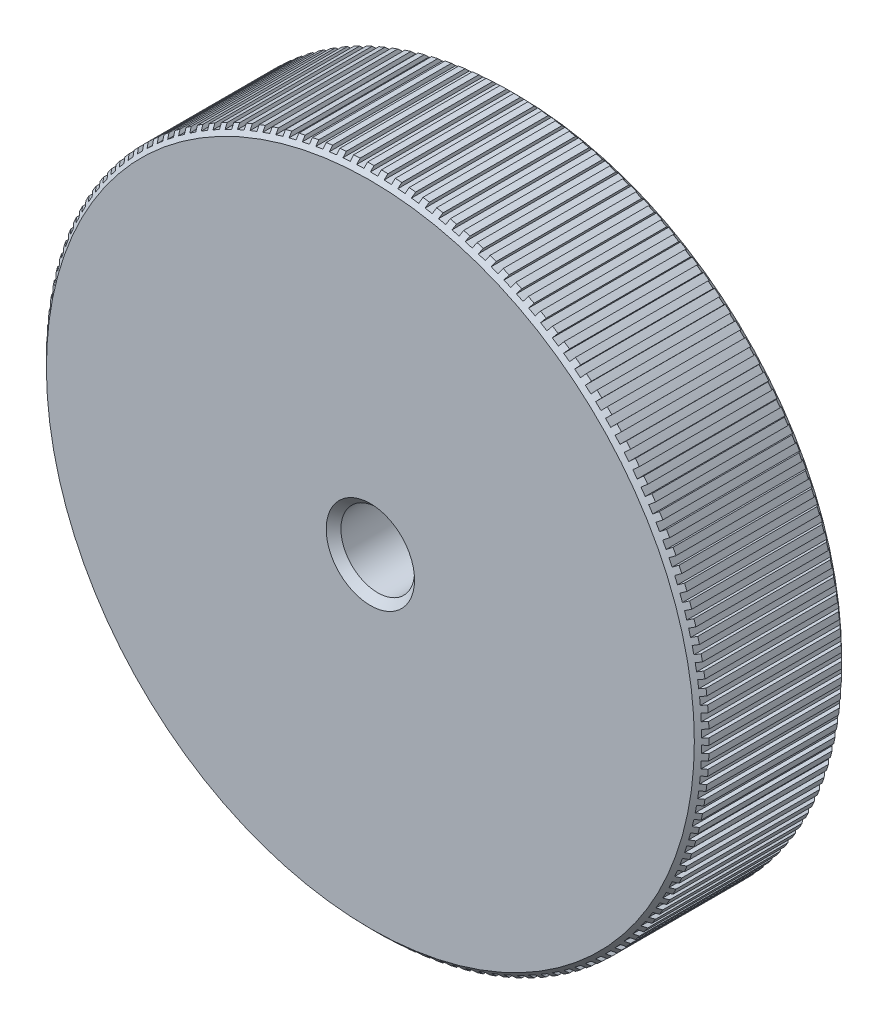
SolidWorks part; units mm, degrees
ref_plane "前视基准面" through (0, 0, 0) normal (0, 0, 1) x (1, 0, 0)
ref_plane "上视基准面" through (0, 0, 0) normal (0, 1, 0) x (1, 0, 0)
ref_plane "右视基准面" through (0, 0, 0) normal (1, 0, 0) x (0, 0, -1)
sketch "草图1" plane through (0, 0, 0) normal (0, 0, 1) x (1, 0, 0)
  circle A0 centre (0, 0) radius 4.5
  dimension "D1" = 9
extrude "凸台-拉伸1" add sketch "草图1" against normal blind 2
sketch "草图2" plane through (0, 0, -2) normal (0, 0, -1) x (-1, 0, 0)
  circle A0 centre (0, 0) radius 2
  dimension "D1" = 4
extrude "凸台-拉伸2" add sketch "草图2" along normal blind 1 contours A0
sketch "草图3" plane through (0, 0, -3) normal (0, 0, -1) x (-1, 0, 0)
  circle A0 centre (0, 0) radius 0.5
  dimension "D1" = 1
extrude "切除-拉伸1" cut sketch "草图3" against normal through all contours A0
cosmetic thread "装饰螺纹线1" parameters "D2"=1
chamfer "倒角1" distance 0.1 angle 45 5 edges at (-2, 0, -3) (4.5, 0, -2) (4.5, 0, 0) (-0.5, 0, 0) (-0.5, 0, -3)
sketch "草图7" plane through (0, 0, 0) normal (0, 0, 1) x (1, 0, 0)
  line L1 (-0.05, -4.9868) -> (0.05, -4.9868)
  line L2 (-0.05, -4.9868) -> (-0.05, 4.9868)
  line L3 (-0.05, 4.9868) -> (0.05, 4.9868)
  line L4 (0.05, -4.9868) -> (0.05, 4.9868)
  line L5 (-0.05, -4.9868) -> (0.05, 4.9868) construction
  line L6 (-0.05, 4.9868) -> (0.05, -4.9868) construction
  circle A0 centre (0, 0) radius 4.45
  point P0 (0, 0)
  dimension "D1" = 8.9
  dimension "D2" = 0.1
extrude "切除-拉伸2" cut sketch "草图7" against normal through all contours A0 L4 L3 L2 region at (0, 4.7183, 0)
pattern_circular "阵列(圆周)1" count 150 over 360 about axis through (0, 0, 0) along (0, 0, -1) of "切除-拉伸2"
